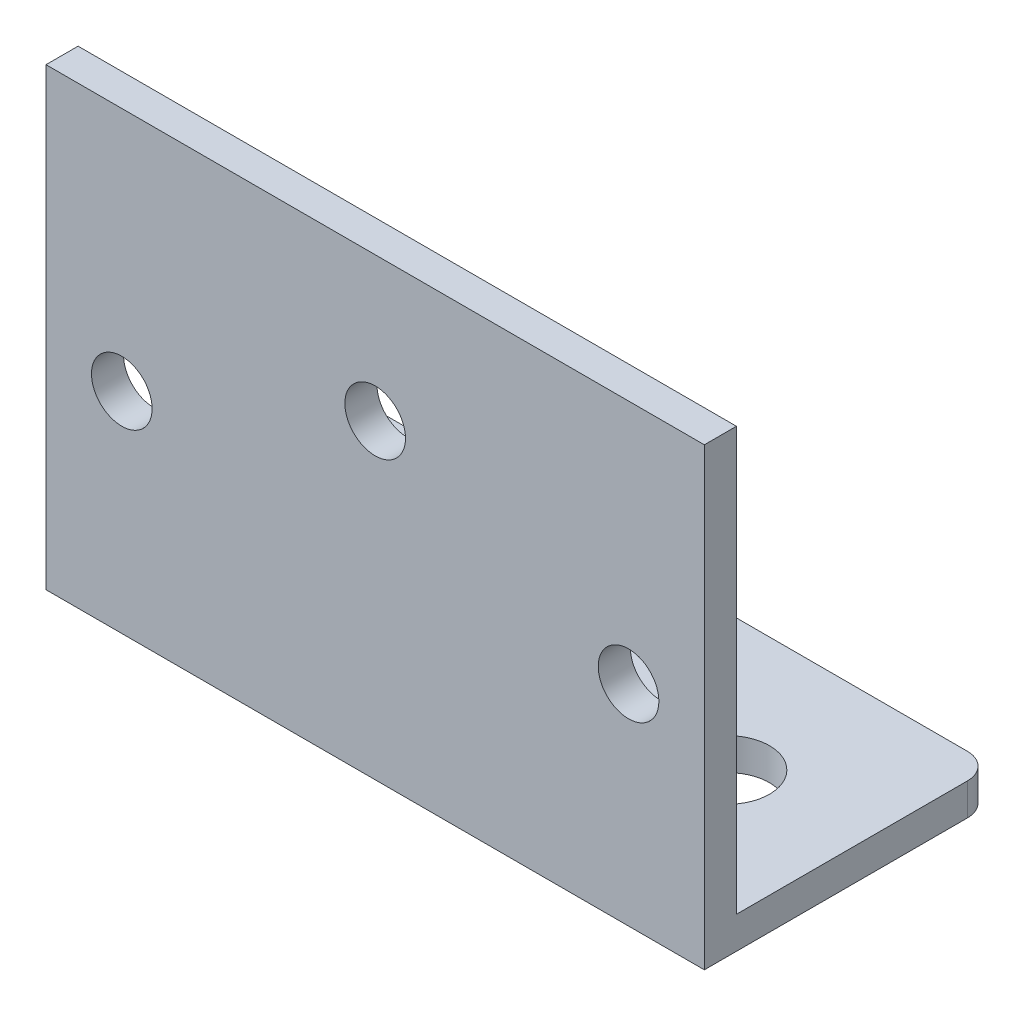
SolidWorks part; units mm, degrees
ref_plane "Front Plane" through (0, 0, 0) normal (0, 0, 1) x (1, 0, 0)
ref_plane "Top Plane" through (0, 0, 0) normal (0, 1, 0) x (1, 0, 0)
ref_plane "Right Plane" through (0, 0, 0) normal (1, 0, 0) x (0, 0, -1)
sketch "Sketch1" plane through (0, 0, 0) normal (0, 0, 1) x (1, 0, 0)
  line L5 (32.5247, -81.1853) -> (32.5247, -36.1853)
  line L6 (-99.1774, -81.1853) -> (98.5881, -81.1853) construction
  line L7 (-32.6263, -81.1853) -> (32.5247, -81.1853)
  line L8 (-32.6263, -36.1853) -> (-32.6263, -81.1853)
  line L9 (32.5247, -36.1853) -> (-32.6263, -36.1853) construction
  line L10 (-23.8633, -27.4223) -> (-47.4269, -27.4223)
  line L11 (-47.4269, -27.4223) -> (-47.4269, -55.4223)
  line L12 (-47.4269, -55.4223) -> (-79.3341, -55.4223)
  line L13 (-47.4269, -55.4223) -> (-47.4269, -70.4223)
  line L14 (-32.6263, -55.4223) -> (32.5247, -55.4223)
  line L15 (-32.6263, -70.4223) -> (32.5247, -70.4223)
  line L16 (-32.6263, -70.4223) -> (-25.1263, -70.4223)
  line L17 (-32.6263, -70.4223) -> (32.5247, -70.4223)
  line L18 (-32.6263, -70.4223) -> (-32.6263, -55.4223)
  line L19 (-32.6263, -55.4223) -> (32.5247, -55.4223)
  line L20 (32.5247, -70.4223) -> (32.5247, -55.4223)
  line L21 (-25.1263, -70.4223) -> (-25.1263, -60.4223)
  line L22 (-0.0508, -55.4223) -> (-0.0508, -70.4223)
  line L23 (32.5247, -36.1853) -> (-32.6263, -36.1853)
  line L24 (-32.6263, -36.1853) -> (-32.6263, -55.4223)
  line L25 (-32.6263, -55.4223) -> (32.5247, -55.4223)
  line L26 (32.5247, -55.4223) -> (32.5247, -36.1853)
  line L27 (32.5247, -55.4223) -> (-32.6263, -55.4223)
  line L28 (32.5247, -55.4223) -> (32.5247, -36.1853)
  line L29 (-32.6263, -55.4223) -> (-32.6263, -36.1853)
  line L30 (32.5247, -36.1853) -> (-32.6263, -36.1853)
  arc A0 (32.5247, -36.1853) -> (14.9987, -36.1853) centre (23.7617, -36.1853) ccw
  arc A1 (-15.1003, -36.1853) -> (14.9987, -36.1853) centre (-0.0508, -36.1853) ccw
  arc A2 (-15.1003, -36.1853) -> (-32.6263, -36.1853) centre (-23.8633, -36.1853) ccw
  circle A5 centre (-47.4269, -16.1853) radius 7.25
  circle A7 centre (-23.8633, -36.1853) radius 5.2324
  circle A8 centre (23.7617, -36.1853) radius 5.2324
  circle A9 centre (-25.1263, -60.4223) radius 3
  circle A10 centre (25.0247, -60.4223) radius 3
  circle A11 centre (-0.0508, -50.4223) radius 3
  dimension "D2" = 10.4648
  dimension "D4" = 8.763
  dimension "D5" = 10
  dimension "D1" = 45
  dimension "D3" = 47.625
  dimension "D6" = 10
  dimension "D7" = 15
extrude "Boss-Extrude1" add sketch "Sketch1" along normal blind 3.175 contours L15 L8 L7 L5 L17 | L19 L22 L17 L5 A10 | A9 L15 L22 L14 L8 | A11 A1 L23 A7 L8 L14 L19 L5 A8 | A11 A1 L30 | L30 A8 | L30 A7 region at (-0.0508, -75.8038, 0) region at (15.6972, -63.0758, 0) region at (16.237, -54.743, 0) region at (-15.7988, -63.0758, 0) region at (23.7617, -38.406, 0) region at (-0.0508, -42.1932, 0) region at (-23.8633, -38.406, 0)
sketch "Sketch2" plane through (0, 0, 0) normal (0, 0, -1) x (-1, 0, 0)
  line L0 (32.6263, -81.1853) -> (-32.5247, -81.1853) construction
  line L1 (32.6263, -81.1853) -> (-32.5247, -81.1853)
  line L3 (-32.5247, -81.1853) -> (32.6263, -81.1853)
  line L4 (-32.5247, -81.1853) -> (-32.5247, -78.0103)
  line L5 (-32.5247, -78.0103) -> (32.6263, -78.0103)
  line L6 (32.6263, -81.1853) -> (32.6263, -78.0103)
  line L7 (32.6263, -14.5103) -> (32.6263, -81.1853) construction
  dimension "D1" = 3.175
  dimension "D2" = 65.151
extrude "Boss-Extrude2" add sketch "Sketch2" along normal blind 25.4 contours L4 L5 L6 L3
fillet "Fillet1" radius 2.54 2 edges at (-32.6263, -79.5978, -25.4) (32.5247, -79.5978, -25.4)
sketch "Sketch3" plane through (0, -78.0103, 0) normal (0, 1, 0) x (1, 0, 0)
  line L0 (-20.2946, 25.4) -> (-20.2946, 11.9193)
  line L4 (29.9847, 25.4) -> (-30.0863, 25.4) construction
  line L8 (19.7054, 25.4) -> (19.7054, 11.9193)
  circle A1 centre (19.7054, 15.0943) radius 4 construction
  circle A12 centre (19.7054, 11.9193) radius 4.1672
  circle A13 centre (-20.2946, 11.9193) radius 4.1672
  point P8 (19.7054, 15.0943)
  point P16 (-20.2946, 11.9193)
  dimension "D1" = 13.4807
  dimension "D2" = 13.4807
extrude "Cut-Extrude1" cut sketch "Sketch3" against normal up to surface (3.175 mm away) contours A13 | A12 up to face at (-0.0508, -81.1853, -15.2037)
